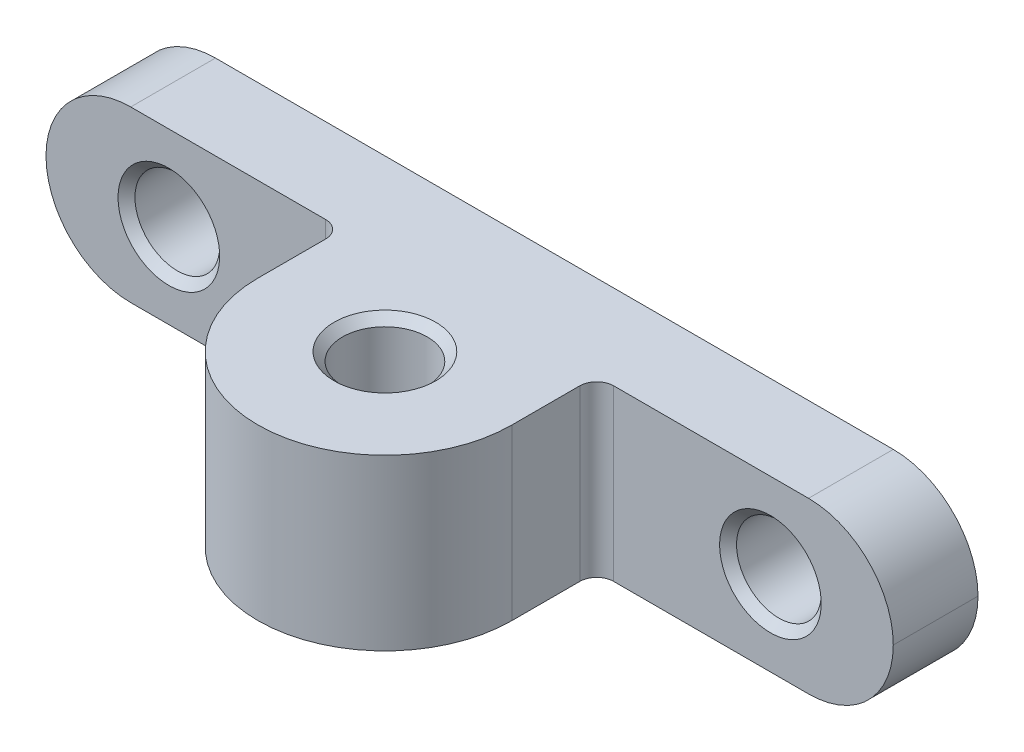
SolidWorks part; units mm, degrees
ref_plane "Front Plane" through (0, 0, 0) normal (0, 0, 1) x (1, 0, 0)
ref_plane "Top Plane" through (0, 0, 0) normal (0, 1, 0) x (1, 0, 0)
ref_plane "Right Plane" through (0, 0, 0) normal (1, 0, 0) x (0, 0, -1)
sketch "Sketch1" plane through (0, 0, 0) normal (0, 1, 0) x (1, 0, 0)
  line L0 (-12.7, 5.08) -> (12.7, 5.08)
  line L1 (12.7, 5.08) -> (12.7, 2.54)
  line L2 (12.7, 2.54) -> (3.81, 2.54)
  line L3 (-12.7, 2.54) -> (-12.7, 5.08)
  line L4 (0, 0) -> (0, 8.4378) construction
  line L5 (3.81, 0) -> (3.81, 2.54)
  line L6 (-3.81, 0) -> (-3.81, 2.54)
  line L7 (-3.81, 2.54) -> (-12.7, 2.54)
  circle A0 centre (0, 0) radius 1.27
  arc A1 (-3.81, 0) -> (3.81, 0) centre (0, 0) ccw
  dimension "D1" = 2.54
  dimension "D2" = 2.54
  dimension "D3" = 5.08
  dimension "D4" = 2.54
  dimension "D5" = 12.7
extrude "Boss-Extrude1" add sketch "Sketch1" along normal blind 5.08
fillet "Fillet1" radius 2.54 4 edges at (-12.7, 5.08, -3.81) (-12.7, 0, -3.81) (12.7, 5.08, -3.81) (12.7, 0, -3.81)
sketch "Sketch2" plane through (0, 0, -2.54) normal (0, 0, 1) x (1, 0, 0)
  line L0 (0, 0) -> (0, 7.8998) construction
  line L2 (-12.7, 2.54) -> (-6.625, 2.54) construction
  circle A0 centre (-9.017, 2.54) radius 1.27
  circle A1 centre (9.017, 2.54) radius 1.27
  point P11 (0, 0)
  point P12 (-7.62, 3.9596)
  dimension "D1" = 2.54
  dimension "D2" = 2.54
  dimension "D3" = 18.034
extrude "Cut-Extrude1" cut sketch "Sketch2" against normal through all both and the other way through all
chamfer "Chamfer1" distance 0.254 angle 45 4 edges at (0, 0, 1.27) (7.747, 2.54, -2.54) (0, 5.08, 1.27) (-10.287, 2.54, -2.54)
fillet "Fillet2" radius 0.508 2 edges at (3.81, 2.54, -2.54) (-3.81, 2.54, -2.54)
